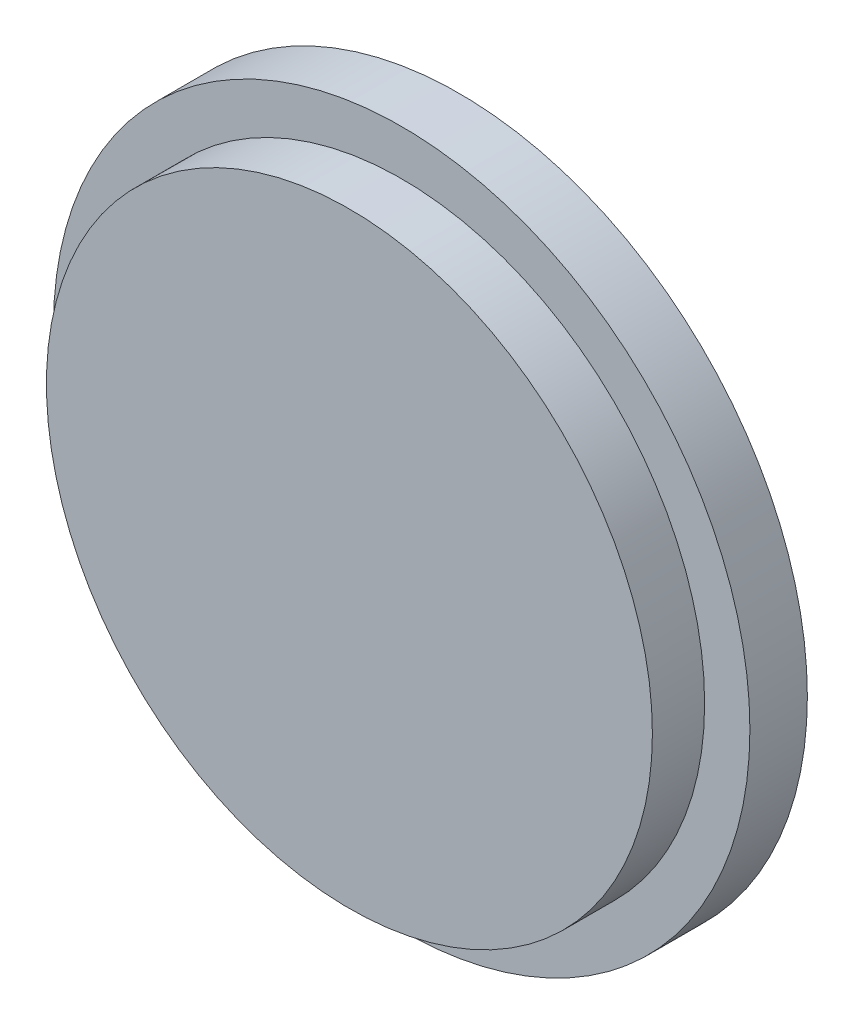
SolidWorks part; units mm, degrees
ref_plane "前视基准面" through (0, 0, 0) normal (0, 0, 1) x (1, 0, 0)
ref_plane "上视基准面" through (0, 0, 0) normal (0, 1, 0) x (1, 0, 0)
ref_plane "右视基准面" through (0, 0, 0) normal (1, 0, 0) x (0, 0, -1)
sketch "草图1" plane through (0, 0, 0) normal (0, 0, 1) x (1, 0, 0)
  circle A0 centre (0, 0) radius 17.4
  circle A1 centre (0, 0) radius 20
  dimension "D1" = 34.8
  dimension "D2" = 40
extrude "凸台-拉伸1" add sketch "草图1" along normal blind 3.3
extrude "凸台-拉伸2" add sketch "草图1<2>" along normal blind 6.3 contours A0 region at (0, 0, 0)
sketch "草图1<2>" plane through (0, 0, 0) normal (0, 0, 1) x (1, 0, 0) same geometry as "草图1"
